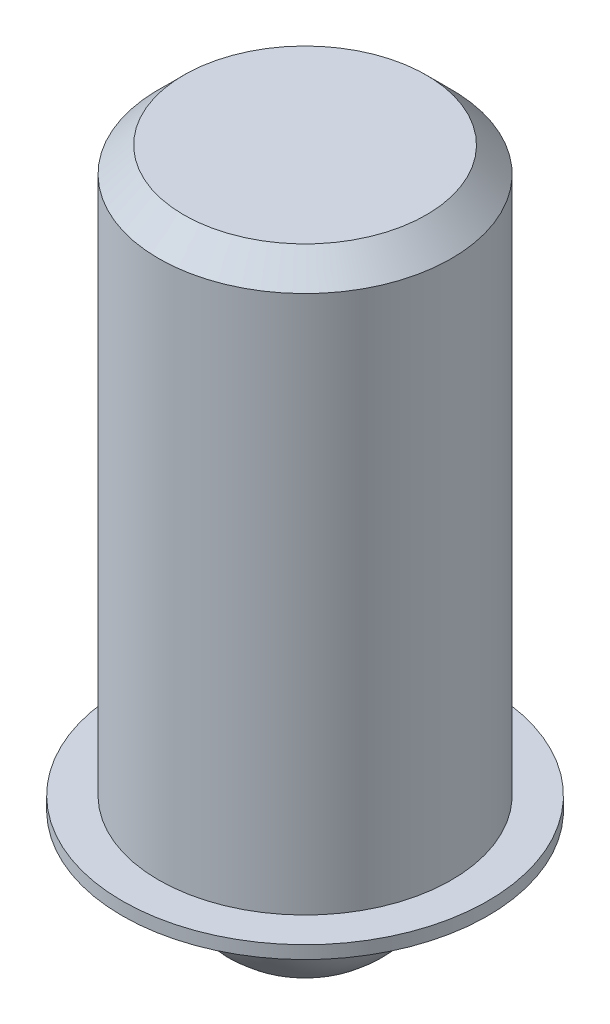
SolidWorks part; units mm, degrees
material "Plain Carbon Steel"
ref_plane "Front" through (0, 0, 0) normal (0, 0, 1) x (1, 0, 0)
ref_plane "Top" through (0, 0, 0) normal (0, 1, 0) x (1, 0, 0)
ref_plane "Right" through (0, 0, 0) normal (1, 0, 0) x (0, 0, -1)
sketch "Sketch24" plane through (0, 0, 0) normal (1, 0, 0) x (0, 0, -1)
  line L5 (0, 7.5565) -> (0, -7.5565) construction
  line L6 (-2.3749, -5.9382) -> (-2.3749, -4.6609) construction
  line L7 (-2.3749, -5.9382) -> (-3.9624, -4.9403) construction
  line L8 (-3.9624, -4.9403) -> (-3.9624, -4.6609)
  line L9 (-3.9624, -4.6609) -> (-3.175, -4.6609)
  line L10 (-3.175, -4.6609) -> (-3.175, 7.0104)
  line L11 (-3.175, 7.0104) -> (-2.6289, 7.5565)
  line L12 (-2.6289, 7.5565) -> (0, 7.5565)
  line L13 (0, -7.5565) -> (0, 7.5565) construction
  line L14 (-3.9624, -4.9403) -> (-2.6289, -5.7785)
  line L15 (-2.6289, -5.7785) -> (-2.6289, -4.6609) construction
  line L16 (-2.6289, -5.7785) -> (-2.3749, -5.7785)
  line L17 (-2.6289, -4.6609) -> (0, -4.6609) construction
  line L18 (0, -4.6609) -> (0, 7.5565)
  line L19 (-2.3749, -5.7785) -> (-2.3749, -4.6609)
  line L20 (-2.3749, -4.6609) -> (0, -4.6609)
  circle A1 centre (0, -5.1816) radius 2.3749 construction
  dimension "Ball Dia" = 4.7498
  dimension "Flange Dia" = 7.9248
  dimension "Body Lg" = 12.2174
  dimension "Body Dia" = 6.35
  dimension "D1" = 0.2794
  dimension "D2" = 45
  dimension "Flange Lg" = 1.1176
  dimension "Ball Projection" = 1.778
  dimension "D3" = 0.254
revolve "Revolve2" add sketch "Sketch24" angle 360 about L5
sketch "Sketch25" plane through (0, 0, 0) normal (1, 0, 0) x (0, 0, -1)
  line L0 (0, -7.5565) -> (0, -2.8067)
  circle A0 centre (0, -5.1816) radius 2.3749 construction
  arc A2 (0, -7.5565) -> (0, -2.8067) centre (0, -5.1816) cw
revolve "Revolve3" add sketch "Sketch25" angle 360 about L18
ref_axis "Center Axis 1" through (0, 8.3122, 0) along (0, -1, 0)
ref_plane "Contact Plane 1" through (0, -4.6609, 0) normal (0, 1, 0) x (1, 0, 0)
equation "\"D1@Sketch24\" = \"Flange Lg@Sketch24\"/4"
